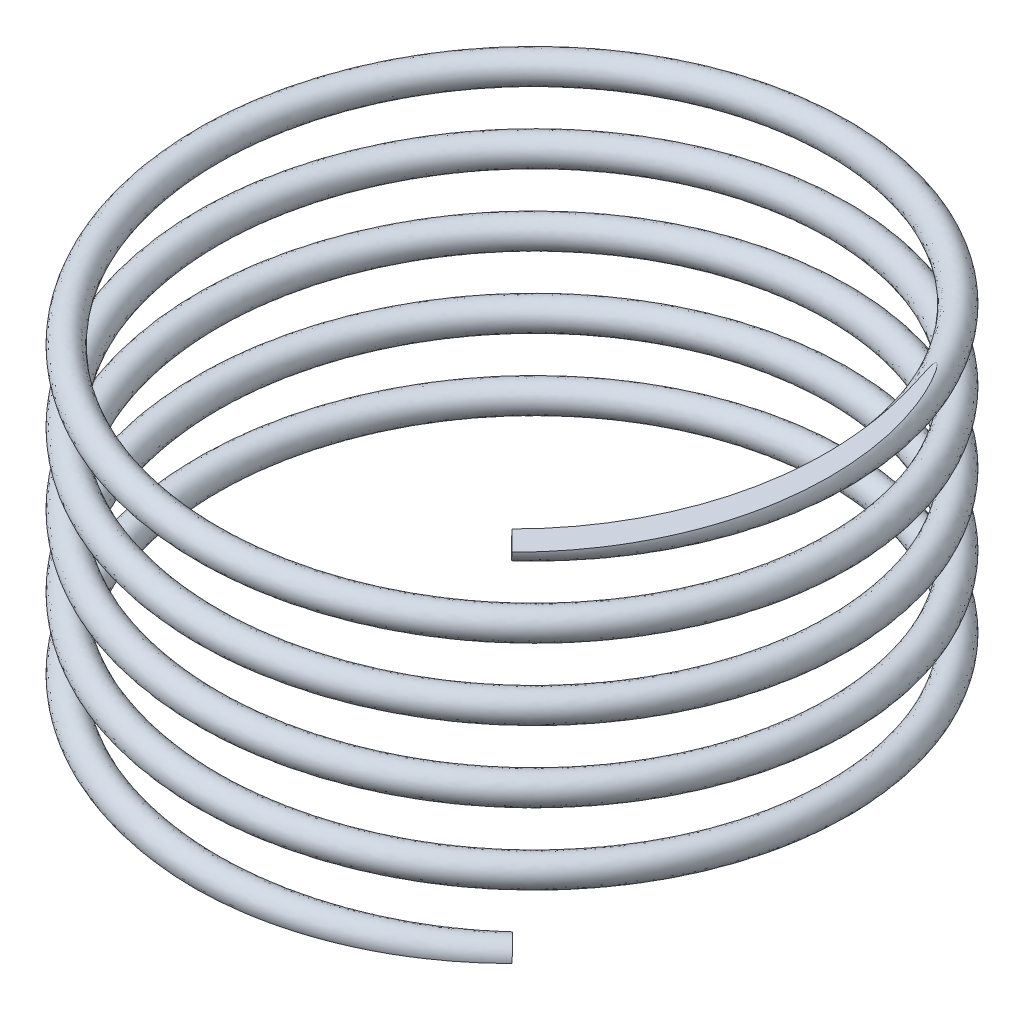
SolidWorks part; units mm, degrees
material "AISI 304"
ref_plane "Front Plane" through (0, 0, 0) normal (0, 0, 1) x (1, 0, 0)
ref_plane "Top Plane" through (0, 0, 0) normal (0, 1, 0) x (1, 0, 0)
ref_plane "Right Plane" through (0, 0, 0) normal (1, 0, 0) x (0, 0, -1)
sketch "Sketch1" plane through (0, 0, 0) normal (0, 1, 0) x (1, 0, 0)
  circle A0 centre (0, 0) radius 8.85
  dimension "D1" = 17.7
curve "Helix/Spiral1" pitch 2 height 10 radius 8.85 left hand yes centre (0, 0, 0) axis (0, -1, 0) start towards (0.7071, 0, 0.7071)
ref_plane "Plane1" through (6.2579, 0, 6.2579) normal (0.7066, -0.0359, -0.7066) x (-0.7074, -0.0555, -0.7046)
sketch "Sketch2" plane through (6.2579, 0, 6.2579) normal (0.7066, -0.0359, -0.7066) x (-0.7074, -0.0555, -0.7046)
  circle A0 centre (0, 0) radius 0.4
  dimension "D1" = 0.8
sweep "Sweep1" add profiles "Sketch2" path "Helix/Spiral1"
sketch "Sketch3" plane through (0, 0, 0) normal (1, 0, 0) x (0, 0, -1)
  line L0 (-9.5, -10) -> (-9.5, 0)
  line L1 (-9.5, -10) -> (9.5, -10)
  line L2 (-9.5, 0) -> (9.5, 0)
  line L3 (9.5, -10) -> (9.5, 0)
  line L4 (-9.5, -10) -> (9.5, 0) construction
  line L5 (-9.5, 0) -> (9.5, -10) construction
  point P1 (0, -5)
  dimension "D1" = 10
  dimension "D2" = 19
extrude "Cut-Extrude1" cut sketch "Sketch3" against normal through all both and the other way through all flip side to cut
sketch "Sketch4" plane through (0, 0, 0) normal (0, 0, 1) x (1, 0, 0)
  line L0 (0, 0) -> (0, -16.19) construction
